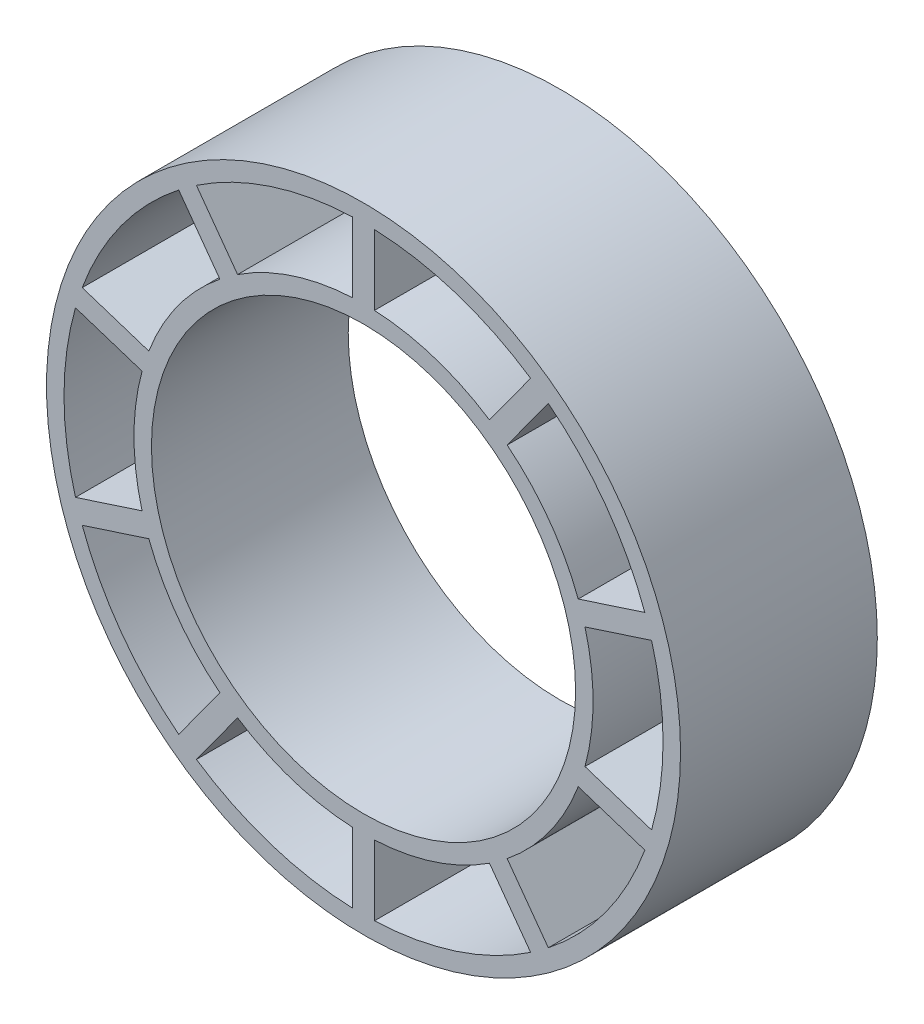
SolidWorks part; units mm, degrees
material "ABS"
ref_plane "Płaszczyzna przednia" through (0, 0, 0) normal (0, 0, 1) x (1, 0, 0)
ref_plane "Płaszczyzna górna" through (0, 0, 0) normal (0, 1, 0) x (1, 0, 0)
ref_plane "Płaszczyzna prawa" through (0, 0, 0) normal (1, 0, 0) x (0, 0, -1)
sketch "Szkic1" plane through (0, 0, 0) normal (0, 0, 1) x (1, 0, 0)
  line L0 (0, 0) -> (51.1373, 70.3845) construction
  line L1 (0, 0) -> (0, 87) construction
  line L2 (0, 52.5) -> (0, 60.5) construction
  line L5 (0, 60.5) -> (0, 68.5) construction
  circle A0 centre (0, 0) radius 60.5 construction
  circle A5 centre (18.6955, 57.5389) radius 1.5
  circle A9 centre (60.5, 0) radius 1.5
  circle A10 centre (18.6955, -57.5389) radius 1.5
  circle A11 centre (-48.9455, -35.561) radius 1.5
  circle A12 centre (-48.9455, 35.561) radius 1.5
  circle A13 centre (0, 0) radius 87 construction
  circle A54 centre (0, 0) radius 72.5
  circle A55 centre (0, 0) radius 48.5
  circle A56 centre (0, 0) radius 52.5
  circle A57 centre (0, 0) radius 68.5
  spline S0 degree 3 poles (0, 87) (18.7775, 85.5429) (47.8143, 75.1785) (35.561, 48.9455) knots 0 0 0 0 1 1 1 1 construction
  spline S1 degree 3 poles (82.7419, 26.8845) (75.5536, 44.2927) (56.7236, 68.7056) (35.561, 48.9455) knots 0 0 0 0 1 1 1 1 construction
  spline S2 degree 3 poles (82.7419, 26.8845) (88.3724, 9.5512) (79.9156, -7.9844) (75.1335, -24.4123) knots 0 0 0 0 1 1 1 1 construction
  spline S3 degree 3 poles (51.1373, -70.3845) (65.8807, -59.6711) (69.3462, -40.5137) (75.1335, -24.4123) knots 0 0 0 0 1 1 1 1 construction
  spline S4 degree 3 poles (51.1373, -70.3845) (36.3923, -81.0957) (17.1016, -78.4715) (0, -79) knots 0 0 0 0 1 1 1 1 construction
  spline S5 degree 3 poles (-51.1373, -70.3845) (-36.3923, -81.0957) (-17.1016, -78.4715) (0, -79) knots 0 0 0 0 1 1 1 1 construction
  spline S6 degree 3 poles (-51.1373, -70.3845) (-65.8807, -59.6711) (-69.3462, -40.5137) (-75.1335, -24.4123) knots 0 0 0 0 1 1 1 1 construction
  spline S7 degree 3 poles (-82.7419, 26.8845) (-88.3724, 9.5512) (-79.9156, -7.9844) (-75.1335, -24.4123) knots 0 0 0 0 1 1 1 1 construction
  spline S8 degree 3 poles (-82.7419, 26.8845) (-77.1088, 44.2169) (-59.9599, 53.4327) (-46.435, 63.9123) knots 0 0 0 0 1 1 1 1 construction
  spline S9 degree 3 poles (0, 87) (-18.2248, 86.9986) (-32.2889, 73.5369) (-46.435, 63.9123) knots 0 0 0 0 1 1 1 1 construction
  point P18 (0, 0)
  point P27 (0, 0)
  point P64 (0, 0)
  point P188 (0, 0)
  dimension "D2" = 145
  dimension "D3" = 97
  dimension "D4" = 3
  dimension "D5" = 4
  dimension "D8" = 174
  dimension "D9" = 36
  dimension "D6" = 4
  dimension "D7" = 5
extrude "Dodanie-wyciągnięcie1" add sketch "Szkic1" along normal blind 4 contours S0 S9 S8 S7 S6 S5 S4 S3 S2 S1 A5 A54 A9 A10 A11 A12 | A56 A55 | A57 A56 | A54 A57 region at (-70.4494, 0, 0) region at (-51.0151, 0, 0) region at (-66.5625, 0, 0)
extrude "Dodanie-wyciągnięcie2" add sketch "Szkic1<3>" along normal blind 45 contours A56 A55 | A54 A57 region at (-70.4494, 0, 0) region at (-51.0151, 0, 0)
sketch "Szkic1<3>" plane through (0, 0, 0) normal (0, 0, 1) x (1, 0, 0) same geometry as "Szkic1"
sketch "Szkic2" plane through (0, 0, 4) normal (0, 0, 1) x (1, 0, 0)
  line L0 (0, 52.5) -> (0, 68.5) construction
  line L1 (-2.5, 52.4404) -> (-2.5, 68.4544)
  line L2 (2.5, 52.4404) -> (2.5, 68.4544)
  line L3 (-2.5, 68.4544) -> (0, 72.2658)
  line L4 (0, 72.2658) -> (2.5, 68.4544)
  line L5 (2.5, 52.4404) -> (0, 48.6291)
  line L6 (0, 48.6291) -> (-2.5, 52.4404)
  circle A0 centre (0, 0) radius 52.5 construction
  circle A1 centre (0, 0) radius 68.5 construction
  circle A2 centre (0, 0) radius 52.5 construction
  dimension "D1" = 2.5
extrude "Dodanie-wyciągnięcie3" add sketch "Szkic2" along normal up to surface (41 mm away) contours L6 L1 L3 L4 L2 L5 up to face at (68.5, 0, 45)
pattern_circular "Szyk kołowy1" count 10 over 360 about axis through (0, 0, 45) along (0, 0, 1) of "Dodanie-wyciągnięcie3"
ref_axis "Oś1" through (0, 0, 53) along (0, 0, -1)
